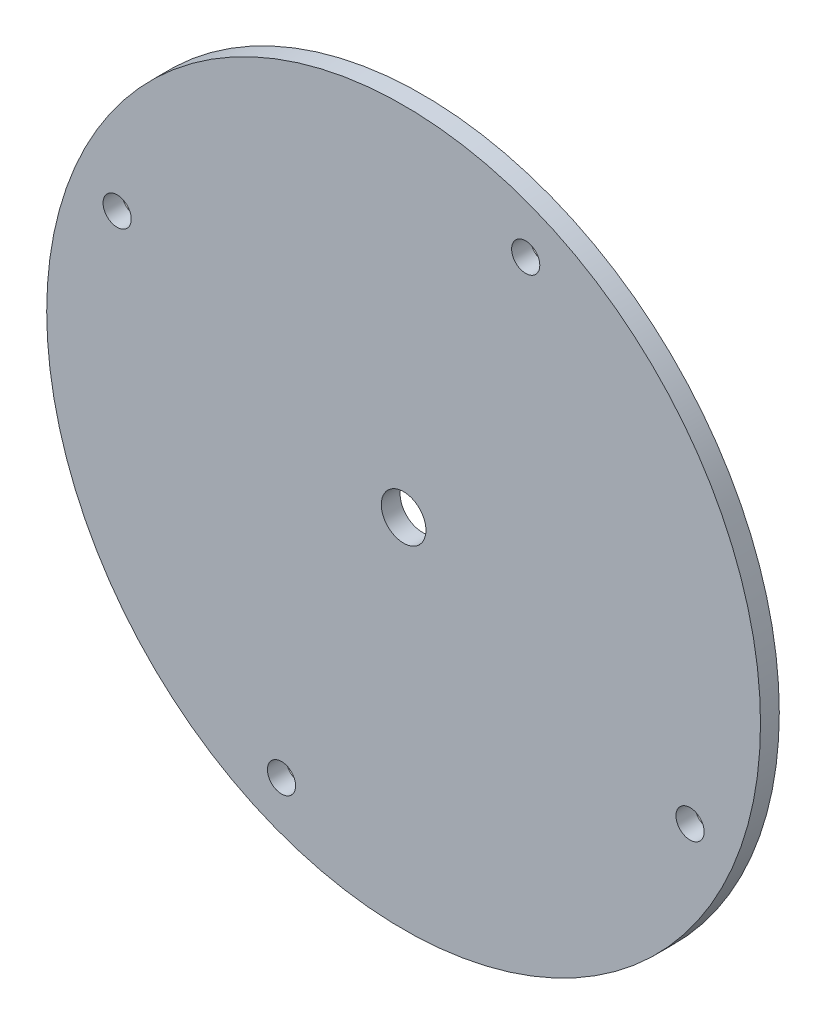
SolidWorks part; units mm, degrees
material "1060 Alloy"
ref_plane "Front Plane" through (0, 0, 0) normal (0, 0, 1) x (1, 0, 0)
ref_plane "Top Plane" through (0, 0, 0) normal (0, 1, 0) x (1, 0, 0)
ref_plane "Right Plane" through (0, 0, 0) normal (1, 0, 0) x (0, 0, -1)
sketch "Sketch1" plane through (0, 0, 0) normal (0, 0, 1) x (1, 0, 0)
  line L5 (50, -50) -> (-50, 50) construction
  line L6 (50, 50) -> (-50, -50) construction
  line L31 (20.5, 61) -> (23.25, 56.2369)
  line L32 (23.25, 56.2369) -> (28.75, 56.2369)
  line L33 (28.75, 56.2369) -> (31.5, 61)
  line L36 (-38.9, 50) -> (38.9, 50) construction
  line L50 (0, -76) -> (0, 122.6166) construction
  line L51 (-76, 0) -> (103.3867, 0) construction
  line L52 (31.5, 61) -> (28.75, 65.7631)
  line L53 (28.75, 65.7631) -> (23.25, 65.7631)
  line L54 (23.25, 65.7631) -> (20.5, 61)
  line L55 (-61, 20.5) -> (-56.2369, 23.25)
  line L56 (-56.2369, 23.25) -> (-56.2369, 28.75)
  line L57 (-56.2369, 28.75) -> (-61, 31.5)
  line L58 (-61, 31.5) -> (-65.7631, 28.75)
  line L59 (-65.7631, 28.75) -> (-65.7631, 23.25)
  line L60 (-65.7631, 23.25) -> (-61, 20.5)
  line L61 (61, -20.5) -> (56.2369, -23.25)
  line L62 (56.2369, -23.25) -> (56.2369, -28.75)
  line L96 (56.2369, -28.75) -> (61, -31.5)
  line L97 (61, -31.5) -> (65.7631, -28.75)
  line L98 (65.7631, -28.75) -> (65.7631, -23.25)
  line L99 (65.7631, -23.25) -> (61, -20.5)
  line L100 (-20.5, -61) -> (-23.25, -56.2369)
  line L101 (-23.25, -56.2369) -> (-28.75, -56.2369)
  line L102 (-28.75, -56.2369) -> (-31.5, -61)
  line L103 (-31.5, -61) -> (-28.75, -65.7631)
  line L104 (-28.75, -65.7631) -> (-23.25, -65.7631)
  line L105 (-23.25, -65.7631) -> (-20.5, -61)
  arc A0 (0, 76) -> (-72.0169, -24.281) centre (0, 0) ccw
  circle A1 centre (26, 61) radius 3
  arc A2 (76, 0) -> (0, 76) centre (0, 0) ccw
  arc A3 (-72.0169, -24.281) -> (0, -76) centre (0, 0) ccw
  arc A4 (0, -76) -> (76, 0) centre (0, 0) ccw
  circle A5 centre (61, -26) radius 3
  circle A6 centre (-26, -61) radius 3
  circle A7 centre (-61, 26) radius 3
  circle A8 centre (26, 61) radius 5.5 construction
  circle A9 centre (-61, 26) radius 5.5 construction
  circle A10 centre (61, -26) radius 5.5 construction
  circle A11 centre (-26, -61) radius 5.5 construction
  dimension "D1" = 152
  dimension "D9" = 26
  dimension "D15" = 11
  dimension "D16" = 11
  dimension "D17" = 11
  dimension "D3" = 26
  dimension "D10" = 26
  dimension "D11" = 26
extrude "Boss-Extrude3" add sketch "Sketch1" along normal blind 4 contours A4 A2 A0 A3 L105 L104 L103 L102 L101 L100 L99 L98 L97 L96 L62 L61 L60 L59 L58 L57 L56 L55 L54 L53 L52 L33 L32 L31 | L59 L60 L55 L56 L57 L58 A7 | L53 L54 L31 L32 L33 L52 A1 | L98 L99 L61 L62 L96 L97 A5 | L104 L105 L100 L101 L102 L103 A6 region at (22.001, 63.3088, 0) region at (-63.3088, 22.001, 0) region at (63.3088, -22.001, 0) region at (-22.001, -63.3088, 0) region at (0, 0, 0)
sketch "Sketch2" plane through (0, 0, 4) normal (0, 0, 1) x (1, 0, 0)
  circle A0 centre (0, 0) radius 4.75
  dimension "D1" = 9.5
extrude "Cut-Extrude1" cut sketch "Sketch2" against normal through all
